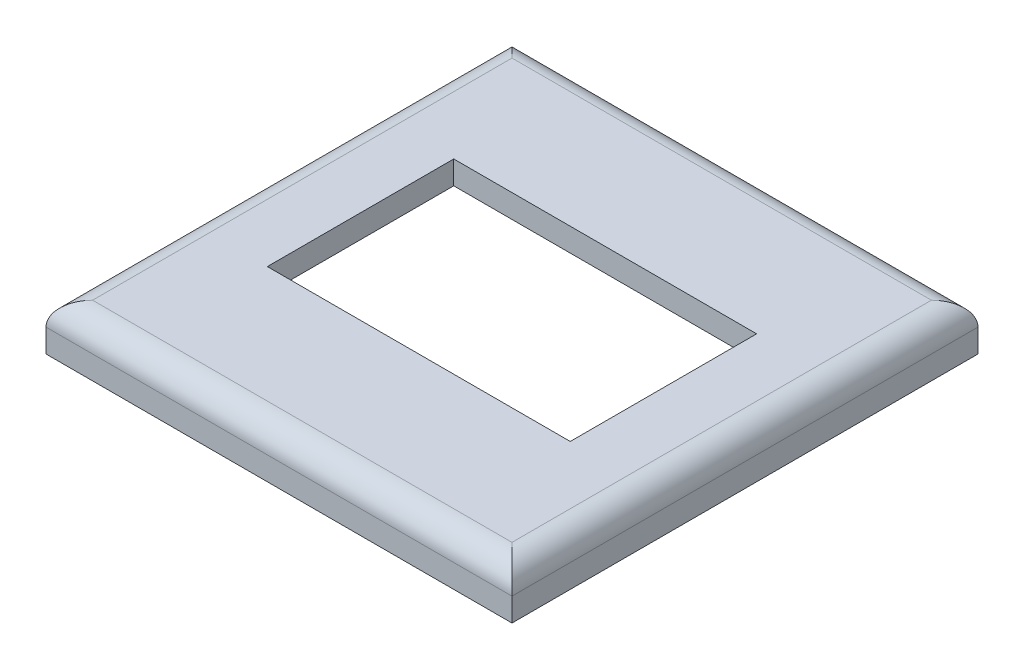
SolidWorks part; units mm, degrees
ref_plane "Front Plane" through (0, 0, 0) normal (0, 0, 1) x (1, 0, 0)
ref_plane "Top Plane" through (0, 0, 0) normal (0, 1, 0) x (1, 0, 0)
ref_plane "Right Plane" through (0, 0, 0) normal (1, 0, 0) x (0, 0, -1)
sketch "Sketch1" plane through (0, 0, 0) normal (0, 1, 0) x (1, 0, 0)
  line L1 (0, 0) -> (40, 0)
  line L2 (0, 0) -> (0, 40)
  line L3 (0, 40) -> (40, 40)
  line L4 (40, 0) -> (40, 40)
  dimension "D1" = 40
  dimension "D2" = 40
extrude "Boss-Extrude1" add sketch "Sketch1" along normal blind 4
fillet "Fillet2" radius 2 4 edges at (20, 4, -40) (40, 4, -20) (20, 4, 0) (0, 4, -20)
shell "Shell1" thickness 2 removed face at (20, 0, -20)
sketch "Sketch2" plane through (0, 4, 0) normal (0, 1, 0) x (1, 0, 0)
  line L0 (2, 38) -> (38, 2) construction
  line L1 (7, 28) -> (33, 28)
  line L2 (7, 28) -> (7, 12)
  line L3 (7, 12) -> (33, 12)
  line L4 (33, 28) -> (33, 12)
  line L5 (7, 12) -> (33, 28) construction
  point P8 (20, 20)
  point P9 (20, 20)
  dimension "D1" = 16
  dimension "D2" = 26
extrude "Cut-Extrude1" cut sketch "Sketch2" against normal blind 4
